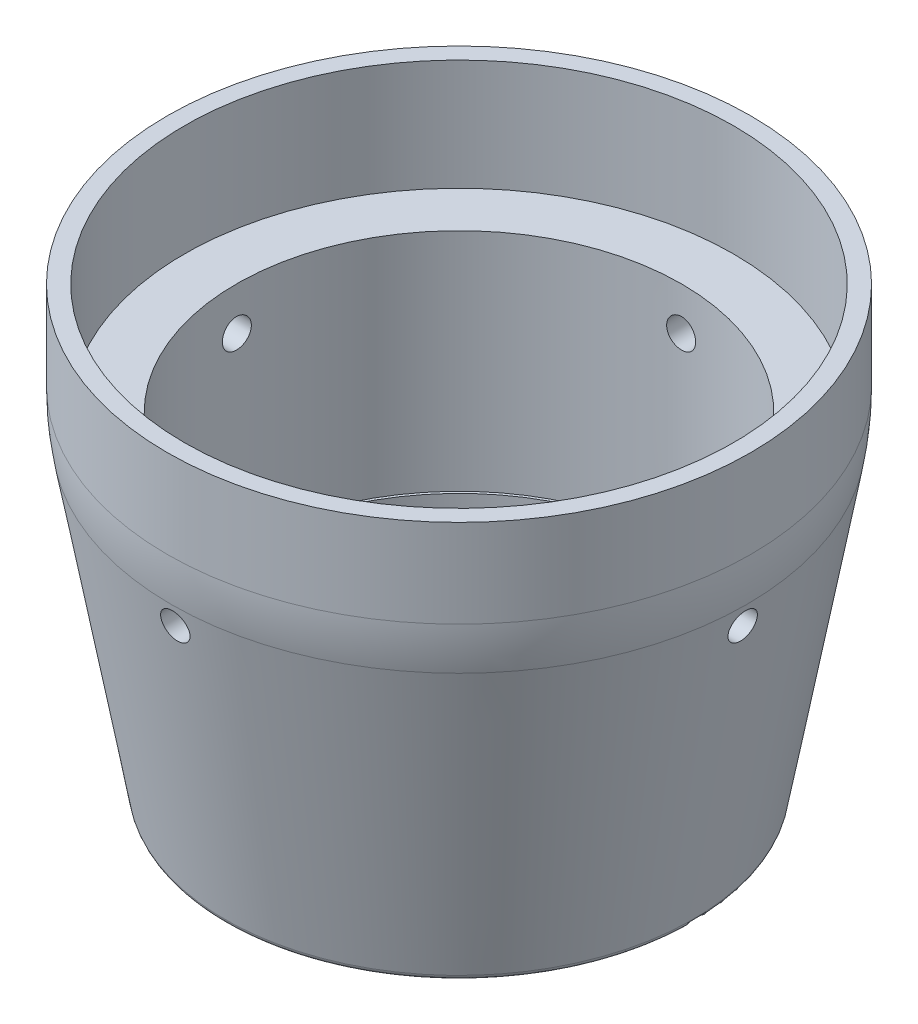
SolidWorks part; units mm, degrees
material "6061-T6 (SS)"
ref_plane "Front Plane" through (0, 0, 0) normal (0, 0, 1) x (1, 0, 0)
ref_plane "Top Plane" through (0, 0, 0) normal (0, 1, 0) x (1, 0, 0)
ref_plane "Right Plane" through (0, 0, 0) normal (1, 0, 0) x (0, 0, -1)
sketch "Sketch2" plane through (0, 0, 0) normal (0, 0, 1) x (1, 0, 0)
  line L8 (22.0472, -22.4282) -> (22.0472, -0.0762)
  line L10 (28.8925, 10.922) -> (28.8925, -0.0762)
  line L11 (28.8925, -0.0762) -> (23.0632, -32.512)
  line L12 (23.0632, -32.512) -> (21.7932, -32.512)
  line L13 (21.7932, -32.512) -> (21.7932, -22.4282)
  line L14 (22.0472, -0.0762) -> (27.1907, -0.0762)
  line L18 (21.7932, -22.4282) -> (22.0472, -22.4282)
  line L19 (27.1907, -0.0762) -> (27.1907, 10.922)
  line L20 (-28.8925, 10.922) -> (28.8925, 10.922) construction
  line L21 (27.1907, 10.922) -> (28.8925, 10.922)
  line L22 (21.717, -32.512) -> (21.717, -22.352) construction
  line L23 (21.971, -22.352) -> (21.971, 7.62) construction
  line L24 (-21.971, -22.352) -> (21.971, -22.352) construction
  line L25 (-27.1145, 0) -> (27.1145, 0) construction
  line L27 (27.1145, 0) -> (27.1145, 10.922) construction
  line L28 (-21.717, -32.512) -> (21.717, -32.512) construction
  dimension "D1" = 0.0762
  dimension "D2" = 0.0762
  dimension "D3" = 0.0762
  dimension "D4" = 0.0762
  dimension "D5" = 0.0762
  dimension "D6" = 1.27
ref_axis "Axis1" through (0, -34.5451, 0) along (0, 1, 0)
revolve "Revolve1" add sketch "Sketch2" angle 360 about axis through (0, -34.5451, 0) along (0, 1, 0)
ref_plane "Plane1" through (0, 0, 28.8925) normal (0, 0, 1) x (1, 0, 0)
sketch "Sketch3" plane through (0, 0, 28.8925) normal (0, 0, 1) x (1, 0, 0)
  line L0 (0, -34.5451) -> (0, 13.0871) construction
  line L2 (28.8925, 10.922) -> (-28.8925, 10.922) construction
  point P0 (0, -4.318)
  dimension "D1" = 15.24
hole_wizard "#6-40 Tapped Hole1" positions "Sketch5" profile "Sketch7" tap size "#6-40" standard "ANSI Inch" end condition up to next
sketch "Sketch5" plane through (0, 0, 28.8925) normal (0, 0, 1) x (1, 0, 0)
  point P0 (0, -4.318)
sketch "Sketch7" plane through (0, -4.318, 28.8925) normal (1, 0, 0) x (0, -1, 0)
  line L0 (0, 0) -> (0, 6.8453)
  line L1 (0, 6.8453) -> (1.4351, 6.8453)
  line L2 (1.4351, 6.8453) -> (1.4351, 0)
  line L5 (1.4351, 0) -> (0, 0)
  line L11 (0, -6.35) -> (0, 107.95) construction
  dimension "Thru Tap Drill Dia." = 2.8702
  dimension "Thru Tap Drill Depth" = 6.8453
pattern_circular "CirPattern1" count 4 over 360 about axis through (0, -34.5451, 0) along (0, -1, 0) of "#6-40 Tapped Hole1"
fillet "Fillet1" radius 0.635 1 edges at (0, -32.512, -23.0632)
fillet "Fillet2" radius 25.4 1 edges at (0, -0.0762, -28.8925)
